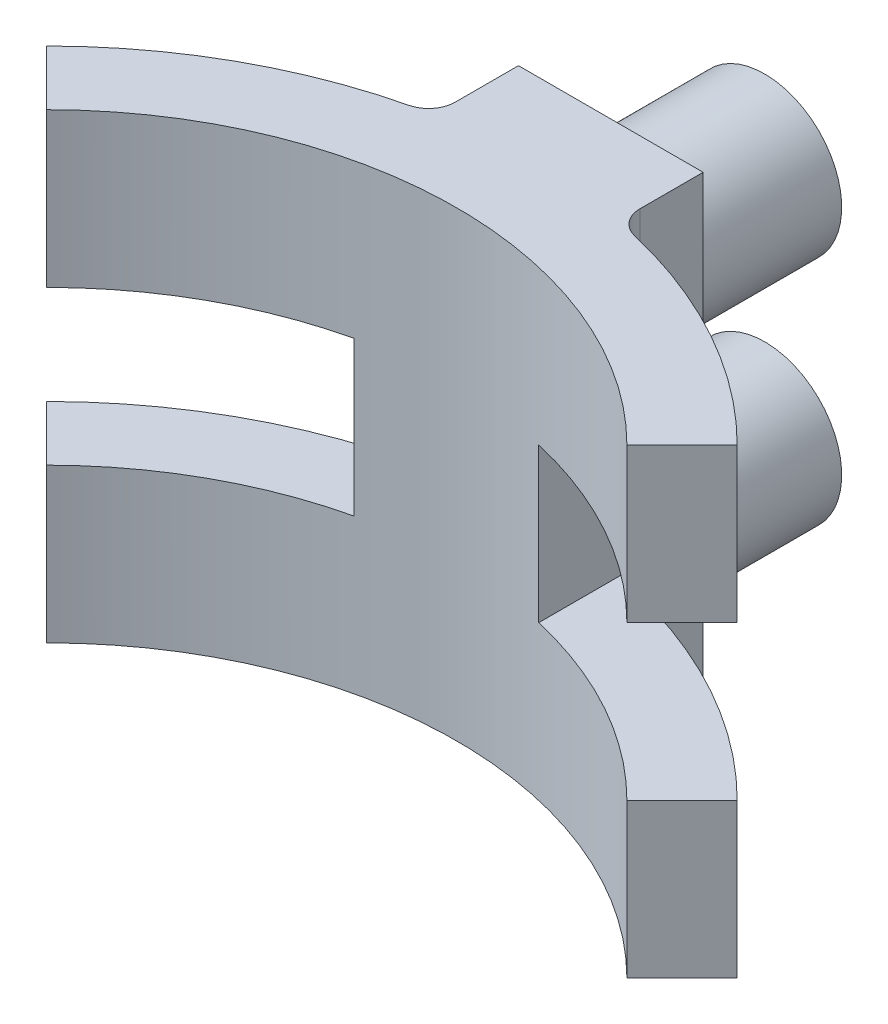
SolidWorks part; units mm, degrees
ref_plane "Front Plane" through (0, 0, 0) normal (0, 0, 1) x (1, 0, 0)
ref_plane "Top Plane" through (0, 0, 0) normal (0, 1, 0) x (1, 0, 0)
ref_plane "Right Plane" through (0, 0, 0) normal (1, 0, 0) x (0, 0, -1)
sketch "Sketch2" plane through (0, 0, 0) normal (0, 1, 0) x (1, 0, 0)
  line L0 (141.4214, 141.4214) -> (168.2914, 168.2914)
  line L1 (-141.4214, 141.4214) -> (-168.2914, 168.2914)
  line L2 (0, 0) -> (0, 275.4734) construction
  line L4 (-45, 244.2069) -> (-45, 275)
  line L5 (45, 244.2069) -> (45, 275)
  line L6 (-45, 275) -> (45, 275)
  line L7 (-45, 275) -> (-168.2914, 168.2914) construction
  line L8 (45, 275) -> (168.2914, 168.2914) construction
  line L9 (-37.5, 275) -> (37.5, 275)
  line L10 (-37.5, 275) -> (-37.5, 362.4021)
  line L11 (37.5, 275) -> (37.5, 362.4021)
  line L12 (-37.5, 362.4021) -> (37.5, 362.4021)
  line L13 (-37.5, 362.4021) -> (-45, 275) construction
  line L14 (37.5, 362.4021) -> (45, 275) construction
  line L15 (-45, 244.2069) -> (-45, 194.8718) construction
  line L16 (45, 244.2069) -> (45, 194.8718) construction
  arc A0 (168.2914, 168.2914) -> (54.996, 231.5587) centre (0, 0) ccw
  arc A1 (141.4214, 141.4214) -> (-141.4214, 141.4214) centre (0, 0) ccw
  arc A2 (-54.996, 231.5587) -> (-168.2914, 168.2914) centre (0, 0) ccw
  arc A3 (-45, 244.2069) -> (-54.996, 231.5587) centre (-58, 244.2069) cw
  arc A4 (45, 244.2069) -> (54.996, 231.5587) centre (58, 244.2069) ccw
  point P17 (-45, 233.7071)
  dimension "D1" = 476
  dimension "D2" = 400
  dimension "D3" = 90
  dimension "D8" = 13
  dimension "D9" = 13
  dimension "D4" = 45
  dimension "D5" = 275
  dimension "D6" = 75
  dimension "D7" = 90
extrude "Boss-Extrude1" add sketch "Sketch2" along normal blind 75 contours A4 L5 L6 L4 A3 A2 L1 A1 L0 A0 region at (0, 0, -209.8855)
extrude "Boss-Extrude2" add sketch "Sketch2<3>" against normal blind 75 from offset 225 separate body contours A1 L1 A2 A3 L4 L6 L5 A4 A0 L0
sketch "Sketch2<3>" plane through (0, 0, 0) normal (0, 1, 0) x (1, 0, 0) same geometry as "Sketch2"
sketch "Sketch4" plane through (0, 0, -275) normal (0, 0, -1) x (-1, 0, 0)
  line L0 (-45, 225) -> (45, 225)
  line L1 (-45, 225) -> (-45, 0.4988)
  line L2 (45, 225) -> (45, 0.4988)
  line L3 (-45, 0.4988) -> (45, 0.4988)
  line L4 (0, 56) -> (0, 0) construction
  line L5 (0, 169) -> (0, 225) construction
  line L6 (-45, 150) -> (45, 150)
  line L7 (-45, 75) -> (45, 75)
  circle A0 centre (0, 169) radius 37.5
  circle A1 centre (0, 56) radius 37.5
  line M11 (45, 75) -> (-45, 75)
  dimension "D2" = 75
  dimension "D3" = 75
  dimension "D1" = 113
extrude "Boss-Extrude4" add sketch "Sketch4" against normal up to surface (80.1282 mm away) contours L6 A0 | L7 A1 | A1 L2 L6 A0 L1 M11 region at (0, 112.5, -275) region at (0, 142.4172, -275) region at (0, 82.5828, -275) up to face at (0, 187.5, -170.7107)
extrude "Boss-Extrude5" add sketch "Sketch4<6>" along normal blind 75 contours L6 A0 | L6 A0 | L7 A1 | L7 A1 region at (0, 175.3099, -275) region at (0, 142.4172, -275) region at (0, 82.5828, -275) region at (0, 49.6901, -275)
sketch "Sketch4<6>" plane through (0, 0, -275) normal (0, 0, -1) x (-1, 0, 0) same geometry as "Sketch4"
